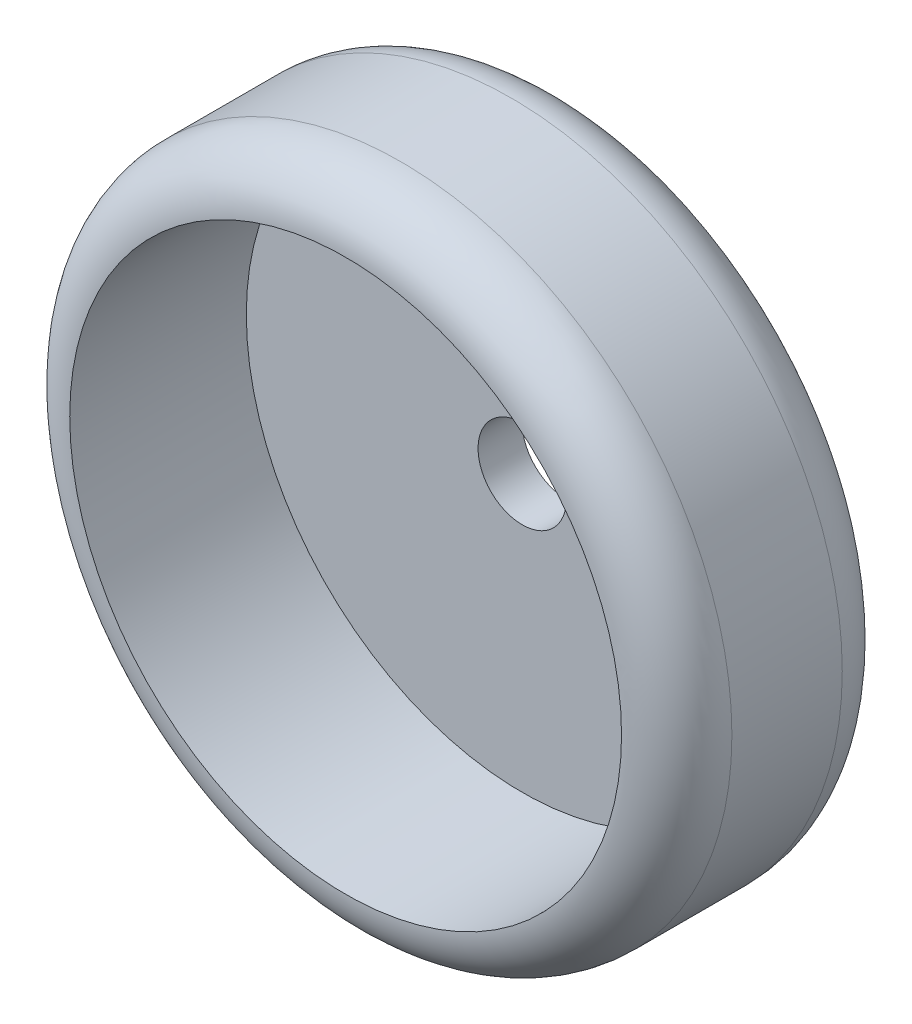
SolidWorks part; units mm, degrees
ref_plane "前视基准面" through (0, 0, 0) normal (0, 0, 1) x (1, 0, 0)
ref_plane "上视基准面" through (0, 0, 0) normal (0, 1, 0) x (1, 0, 0)
ref_plane "右视基准面" through (0, 0, 0) normal (1, 0, 0) x (0, 0, -1)
other "Configuration Table"
sketch "草图1" plane through (0, 0, 0) normal (0, 0, 1) x (1, 0, 0)
  circle A0 centre (0, 0) radius 30
  circle A1 centre (0, 0) radius 4
extrude "凸台-拉伸1" add sketch "草图1" along normal blind 20
sketch3d "3D草图1"
  point P0 (-1.4379, -4.8957, 20)
ref_plane "基准面1" through (0, 0, 20) normal (0, 0, 1) x (1, 0, 0)
sketch "草图2" plane through (0, 0, 20) normal (0, 0, 1) x (1, 0, 0)
  circle A0 centre (0, 0) radius 25
extrude "切除-拉伸1" cut sketch "草图2" against normal blind 16
fillet "圆角1" radius 5 2 edges at (30, 0, 0) (30, 0, 20)
